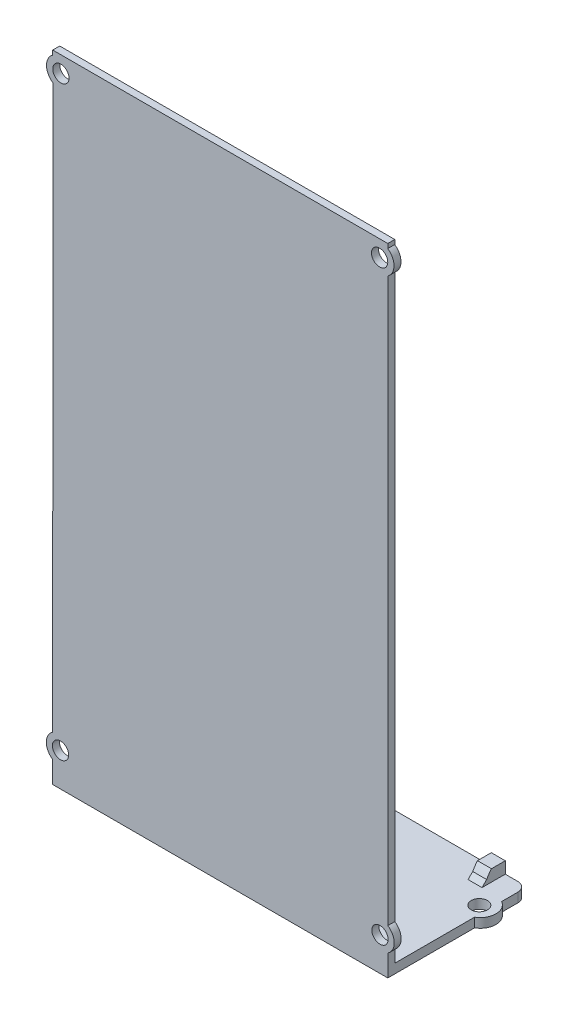
SolidWorks part; units mm, degrees
ref_plane "Front Plane" through (0, 0, 0) normal (0, 0, 1) x (1, 0, 0)
ref_plane "Top Plane" through (0, 0, 0) normal (0, 1, 0) x (1, 0, 0)
ref_plane "Right Plane" through (0, 0, 0) normal (1, 0, 0) x (0, 0, -1)
sketch "Sketch1" plane through (0, 0, 0) normal (0, 0, 1) x (1, 0, 0)
  line L0 (-31.5, -134.5) -> (31.5, -134.5)
  line L28 (-35.994, -6.0543) -> (-36, -126.951)
  line L29 (-36, -132.049) -> (-36, -134.5)
  line L30 (-36, -134.5) -> (-31.5, -134.5)
  line L31 (-31.5, -134.5) -> (-31.5, -132.049) construction
  line L32 (-31.5, -126.951) -> (-31.5, -7) construction
  line L33 (-31.5, -7) -> (31.5, -7) construction
  line L34 (31.5, -7) -> (31.5, -126.951) construction
  line L35 (31.5, -132.049) -> (31.5, -134.5) construction
  line L36 (31.5, -134.5) -> (36, -134.5)
  line L37 (36, -134.5) -> (36, -132.049)
  line L38 (36, -126.951) -> (36, -6.049)
  line L39 (36, -0.951) -> (36, 0)
  line L40 (36, 0) -> (-36, 0)
  line L41 (-36, 0) -> (-36, -0.951)
  circle A0 centre (-34.3286, -129.5) radius 1.75
  circle A1 centre (34.3232, -129.5) radius 1.75
  circle A2 centre (34.2427, -3.5) radius 1.75
  circle A3 centre (-34.2441, -3.5006) radius 1.75
  arc A12 (-36, -126.951) -> (-36, -132.049) centre (-34.3286, -129.5) ccw
  arc A13 (-31.5, -132.049) -> (-31.5, -126.951) centre (-34.3286, -129.5) ccw construction
  arc A14 (31.5, -126.951) -> (31.5, -132.049) centre (34.3232, -129.5) ccw construction
  arc A15 (36, -132.049) -> (36, -126.951) centre (34.3232, -129.5) ccw
  arc A16 (36, -6.049) -> (36, -0.951) centre (34.2427, -3.5) ccw
  arc A17 (-36, -0.951) -> (-35.994, -6.0543) centre (-34.2441, -3.5006) ccw
  dimension "D2" = 3.5
extrude "Boss-Extrude1" add sketch "Sketch1" along normal blind 1.5
sketch "Sketch2" plane through (-36, 0, 0) normal (-1, 0, 0) x (0, 0, 1)
  line L0 (1.5, -134.5) -> (1.5, -136.7)
  line L1 (1.5, -136.7) -> (-40, -136.7)
  line L2 (-40, -136.7) -> (-40, -134.7)
  line L3 (-40, -134.7) -> (0, -134.7)
  line L4 (0, -134.7) -> (0, -134.5)
  line L10 (0, -132.049) -> (0, -134.5)
  line L11 (0, -134.5) -> (1.5, -134.5)
  line L12 (1.5, -134.5) -> (1.5, -132.049)
  line L13 (1.5, -132.049) -> (0, -132.049)
  line L14 (0, -132.049) -> (0, -134.5)
  line L16 (1.5, -134.5) -> (1.5, -132.049)
  line L17 (1.5, -132.049) -> (0, -132.049)
  dimension "D1" = 2
  dimension "D2" = 0.2
  dimension "D4" = 40
  dimension "D3" = 0
extrude "Boss-Extrude2" add sketch "Sketch2" against normal up to surface (72 mm away) up to face at (36, -133.2745, 0.75)
sketch "Sketch3" plane through (0, 0, 0) normal (1, 0, 0) x (0, 0, -1)
  line L0 (0, -119.7) -> (15, -134.7)
  line L1 (0, -126.951) -> (0, -6.049) construction
  line L2 (40, -134.7) -> (0, -134.7) construction
  line L3 (15, -134.7) -> (0, -134.7)
  line L4 (0, -134.7) -> (0, -119.7)
  dimension "D1" = 15
extrude "Boss-Extrude3" add sketch "Sketch3" along normal blind 1.5 and the other way blind 1.5
sketch "Sketch4" plane through (0, -136.7, 0) normal (0, -1, 0) x (1, 0, 0)
  line L0 (-36, -17.1528) -> (-36, -22.963)
  line L1 (36, -17.1528) -> (36, -22.963)
  line L2 (-36, -40) -> (-36, 1.5) construction
  line L4 (36, 1.5) -> (36, -40) construction
  arc A2 (-36, -17.1528) -> (-36, -22.963) centre (-34.2684, -20.0579) ccw
  arc A3 (36, -22.963) -> (36, -17.1528) centre (34.3298, -20.0579) ccw
extrude "Boss-Extrude4" add sketch "Sketch4" against normal blind 2
sketch "Sketch5" plane through (0, -136.7, 0) normal (0, -1, 0) x (1, 0, 0)
  line L0 (-37.6504, -20.0579) -> (-36.0004, -20.0579) construction
  line L1 (36.0308, -20.0579) -> (37.6808, -20.0579) construction
  circle A0 centre (-34.2539, -19.9468) radius 1.75
  circle A1 centre (34.289, -19.8892) radius 1.75
  arc A2 (-36, -17.1528) -> (-36, -22.963) centre (-34.2684, -20.0579) ccw construction
  arc A3 (36, -22.963) -> (36, -17.1528) centre (34.3298, -20.0579) ccw construction
  point P6 (-37.6504, -20.0579)
  point P7 (-36.0004, -20.0579)
  dimension "D1" = 3.5
  dimension "D2" = 1.65
extrude "Cut-Extrude1" cut sketch "Sketch5" against normal blind 2
sketch "Sketch6" plane through (0, -136.7, 0) normal (0, -1, 0) x (1, 0, 0)
  line L0 (-36.784, -28.4468) -> (36, -28.4468)
  point P0 (-34.2539, -19.9468)
  dimension "D1" = 8.5
extrude "Cut-Extrude2" cut sketch "Sketch6" against normal through all and the other way through all
sketch "Sketch7" plane through (0, -136.7, 0) normal (0, -1, 0) x (1, 0, 0)
  line L0 (-36, -28.4468) -> (36, -28.4468) construction
  line L1 (-31.3, -28.4468) -> (-28.3, -28.4468)
  line L2 (-31.3, -28.4468) -> (-31.3, -24.4468)
  line L3 (-31.3, -24.4468) -> (-28.3, -24.4468)
  line L4 (-28.3, -28.4468) -> (-28.3, -24.4468)
  line L5 (-36, -25.7049) -> (-31.3, -25.7049) construction
  line L6 (31.3, -28.4468) -> (28.3, -28.4468)
  line L7 (31.3, -28.4468) -> (31.3, -24.4468)
  line L8 (31.3, -24.4468) -> (28.3, -24.4468)
  line L9 (28.3, -28.4468) -> (28.3, -24.4468)
  line L10 (-36, -28.4468) -> (-36, -22.963) construction
  line L11 (31.3, -24.4468) -> (36, -24.4468) construction
  line L12 (36, -22.963) -> (36, -28.4468) construction
  dimension "D1" = 4.7
  dimension "D2" = 3
  dimension "D3" = 4
extrude "Boss-Extrude6" add sketch "Sketch7" against normal blind 2.5 from surface at -2 starting at face at (34.289, -134.7, -21.6392)
fillet "Fillet1" radius 2 2 edges at (-36, -135.7, -28.4468) (36, -135.7, -28.4468)
chamfer "Chamfer1" distance 1 angle 45 4 edges at (-29.8, -132.2, -24.4468) (29.8, -132.2, -24.4468) (-29.8, -134.7, -24.4468) (29.8, -134.7, -24.4468)
fillet "Fillet2" radius 8 2 edges at (-29.8, -133.2, -24.4468) (29.8, -133.2, -24.4468)
sketch "Sketch8" plane through (0, -136.7, 0) normal (0, -1, 0) x (1, 0, 0)
  line L0 (-36, -17.1528) -> (-36, 1.5) construction
  line L1 (-31, -5.5) -> (4, -5.5)
  line L2 (-31, -5.5) -> (-31, -25.4468)
  line L3 (-31, -25.4468) -> (4, -25.4468)
  line L4 (4, -5.5) -> (4, -25.4468)
  line L5 (36, 1.5) -> (-36, 1.5) construction
  line L6 (-34, -28.4468) -> (34, -28.4468) construction
  dimension "D1" = 5
  dimension "D2" = 40
  dimension "D3" = 7
  dimension "D4" = 3
extrude "Cut-Extrude3" cut sketch "Sketch8" against normal blind 22.4262
